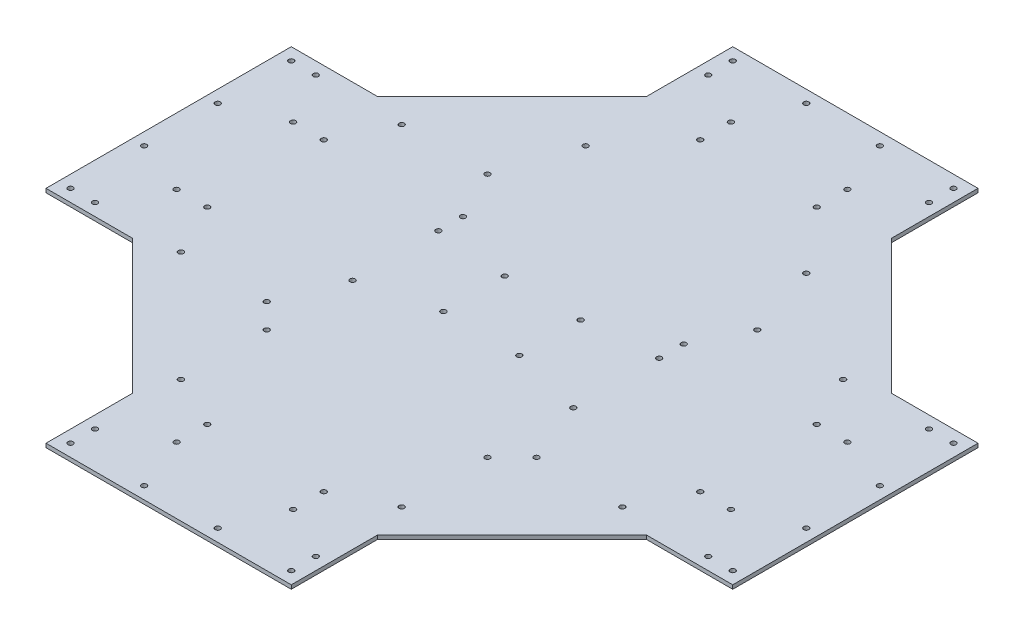
SolidWorks part; units mm, degrees
ref_plane "Front Plane" through (0, 0, 0) normal (0, 0, 1) x (1, 0, 0)
ref_plane "Top Plane" through (0, 0, 0) normal (0, 1, 0) x (1, 0, 0)
ref_plane "Right Plane" through (0, 0, 0) normal (1, 0, 0) x (0, 0, -1)
sketch "Sketch1" plane through (0, 0, 0) normal (0, 1, 0) x (1, 0, 0)
  line L0 (0, -280) -> (100, -280)
  line L1 (100, -280) -> (100, -209.6016)
  line L2 (280, -100) -> (209.6016, -100)
  line L3 (0, 0) -> (0, -280) construction
  line L4 (280, 0) -> (280, -100)
  line L5 (-280, 280) -> (280, 280) construction
  line L6 (-280, 280) -> (-280, -280) construction
  line L7 (-280, -280) -> (280, -280) construction
  line L8 (280, 280) -> (280, -280) construction
  line L9 (-280, 280) -> (280, -280) construction
  line L10 (-280, -280) -> (280, 280) construction
  line L11 (100, -209.6016) -> (209.6016, -100)
  line L12 (-280, 0) -> (-280, -100)
  line L13 (-280, -100) -> (-209.6016, -100)
  line L14 (-209.6016, -100) -> (-100, -209.6016)
  line L15 (-100, -280) -> (-100, -209.6016)
  line L16 (0, -280) -> (-100, -280)
  line L17 (0, 280) -> (-100, 280)
  line L18 (-100, 280) -> (-100, 209.6016)
  line L19 (-100, 209.6016) -> (-209.6016, 100)
  line L20 (-280, 100) -> (-209.6016, 100)
  line L21 (-280, 0) -> (-280, 100)
  line L22 (280, 0) -> (280, 100)
  line L23 (280, 100) -> (209.6016, 100)
  line L24 (209.6016, 100) -> (100, 209.6016)
  line L25 (100, 280) -> (100, 209.6016)
  line L26 (0, 280) -> (100, 280)
  line L27 (111.5258, -219.2889) -> (219.2889, -111.5258) construction
  line L28 (219.2889, -111.5258) -> (247.5732, -139.8101) construction
  line L29 (247.5732, -139.8101) -> (139.8101, -247.5732) construction
  line L30 (139.8101, -247.5732) -> (111.5258, -219.2889) construction
  line L31 (-100, -270) -> (100, -270) construction
  line L32 (-90, -280) -> (-90, 280) construction
  line L33 (-70, -70) -> (70, -70) construction
  line L34 (-70, -70) -> (-70, 70) construction
  line L35 (-70, 70) -> (70, 70) construction
  line L36 (70, -70) -> (70, 70) construction
  line L37 (-70, -70) -> (70, 70) construction
  line L38 (-70, 70) -> (70, -70) construction
  line L39 (-100, -260) -> (100, -260) construction
  line L40 (-280, 40) -> (280, 40) construction
  line L41 (0, 280) -> (0, 0) construction
  line L42 (-280, -90) -> (280, -90) construction
  line L43 (-260, -100) -> (-260, 100) construction
  line L44 (0, 0) -> (-280, 0) construction
  arc A0 (100, -280) -> (280, -100) centre (100, -100) ccw construction
  circle A1 centre (-47.5, -201) radius 2.125
  circle A2 centre (-47.5, -226) radius 2.125
  circle A3 centre (47.5, -226) radius 2.125
  circle A4 centre (47.5, -201) radius 2.125
  circle A5 centre (-201, 47.5) radius 2.125
  circle A6 centre (-226, 47.5) radius 2.125
  circle A7 centre (-201, -47.5) radius 2.125
  circle A8 centre (-226, -47.5) radius 2.125
  circle A9 centre (47.5, 201) radius 2.125
  circle A10 centre (47.5, 226) radius 2.125
  circle A11 centre (-47.5, 201) radius 2.125
  circle A12 centre (-47.5, 226) radius 2.125
  circle A13 centre (201, -47.5) radius 2.125
  circle A14 centre (226, -47.5) radius 2.125
  circle A15 centre (201, 47.5) radius 2.125
  circle A16 centre (226, 47.5) radius 2.125
  circle A17 centre (-90, -270) radius 2.125
  circle A18 centre (-30, -270) radius 2.125
  circle A19 centre (30, -270) radius 2.125
  circle A20 centre (90, -270) radius 2.125
  circle A21 centre (-270, 90) radius 2.125
  circle A22 centre (-270, 30) radius 2.125
  circle A23 centre (-270, -30) radius 2.125
  circle A24 centre (-270, -90) radius 2.125
  circle A25 centre (90, 270) radius 2.125
  circle A26 centre (30, 270) radius 2.125
  circle A27 centre (-30, 270) radius 2.125
  circle A28 centre (-90, 270) radius 2.125
  circle A29 centre (270, -90) radius 2.125
  circle A30 centre (270, -30) radius 2.125
  circle A31 centre (270, 30) radius 2.125
  circle A32 centre (270, 90) radius 2.125
  circle A33 centre (-90, -250) radius 2.125
  circle A34 centre (-90, -180) radius 2.125
  circle A35 centre (-90, -110) radius 2.125
  circle A36 centre (-90, -40) radius 2.125
  circle A37 centre (-90, 30) radius 2.125
  circle A38 centre (-90, 50) radius 2.125
  circle A39 centre (-90, 100) radius 2.125 construction
  circle A40 centre (-90, 150) radius 2.125
  circle A41 centre (-90, 200) radius 2.125 construction
  circle A42 centre (-90, 250) radius 2.125
  circle A43 centre (90, -250) radius 2.125
  circle A44 centre (90, -180) radius 2.125
  circle A45 centre (90, -110) radius 2.125
  circle A46 centre (90, -40) radius 2.125
  circle A47 centre (90, 30) radius 2.125
  circle A48 centre (90, 50) radius 2.125
  circle A49 centre (90, 100) radius 2.125 construction
  circle A50 centre (90, 150) radius 2.125
  circle A51 centre (90, 200) radius 2.125 construction
  circle A52 centre (90, 250) radius 2.125
  circle A53 centre (-250, -90) radius 2.125
  circle A54 centre (-180, -90) radius 2.125
  circle A55 centre (-110, -90) radius 2.125
  circle A56 centre (-110, 90) radius 2.125
  circle A57 centre (-180, 90) radius 2.125
  circle A58 centre (-250, 90) radius 2.125
  circle A59 centre (110, -90) radius 2.125
  circle A60 centre (180, -90) radius 2.125
  circle A61 centre (250, -90) radius 2.125
  circle A62 centre (110, 90) radius 2.125
  circle A63 centre (180, 90) radius 2.125
  circle A64 centre (250, 90) radius 2.125
  point P33 (0, 0)
  point P68 (0, 0)
  point P107 (0, 0)
  dimension "D10" = 25
  dimension "4.25" = 4.25
  dimension "D11" = 4.25
  dimension "D16" = 4.25
  dimension "D24" = 4.25
  dimension "D28" = 4.25
  dimension "D32" = 4.25
  dimension "D1" = 560
  dimension "D2" = 90
  dimension "D3" = 280
  dimension "D4" = 4
  dimension "D5" = 100
  dimension "D6" = 155
  dimension "D7" = 152.4
  dimension "D8" = 15
  dimension "D9" = 40
  dimension "D12" = 47.5
  dimension "D13" = 54
  dimension "D15" = 10
  dimension "D17" = 10
  dimension "D18" = 76.2
  dimension "D19" = 140
  dimension "D20" = 140
  dimension "D23" = 10
  dimension "D25" = 10
  dimension "D26" = 300
  dimension "D29" = 10
  dimension "D31" = 20
  dimension "D33" = 10
  dimension "D21" = 4
  dimension "D27" = 5
  dimension "D30" = 5
  dimension "D34" = 3
  dimension "D14" = 4
  dimension "D22" = 4
extrude "Boss-Extrude1" add sketch "Sketch1" along normal blind 3.175 contours L26 L17 L18 L19 L20 L21 L12 L13 L14 L15 L16 L0 L1 L11 L2 L4 L22 L23 L24 L25 region at (0, 0, -0.0137)
sketch "Sketch2" plane through (0, 3.175, 0) normal (0, 1, 0) x (1, 0, 0)
  line L0 (0, 25.5202) -> (0, -25) construction
  line L1 (-31, -25) -> (31, -25) construction
  line L2 (-31, -25) -> (-31, 25) construction
  line L3 (-31, 25) -> (31, 25) construction
  line L4 (31, -25) -> (31, 25) construction
  line L5 (-31, -25) -> (31, 25) construction
  line L6 (-31, 25) -> (31, -25) construction
  circle A0 centre (-31, 25) radius 2.125
  circle A1 centre (-31, -25) radius 2.125
  circle A2 centre (31, -25) radius 2.125
  circle A3 centre (31, 25) radius 2.125
  point P0 (0, 0)
  dimension "D3" = 4.25
  dimension "D4" = 4.25
  dimension "D1" = 62
  dimension "D2" = 50
extrude "Cut-Extrude1" cut sketch "Sketch2" against normal through all
